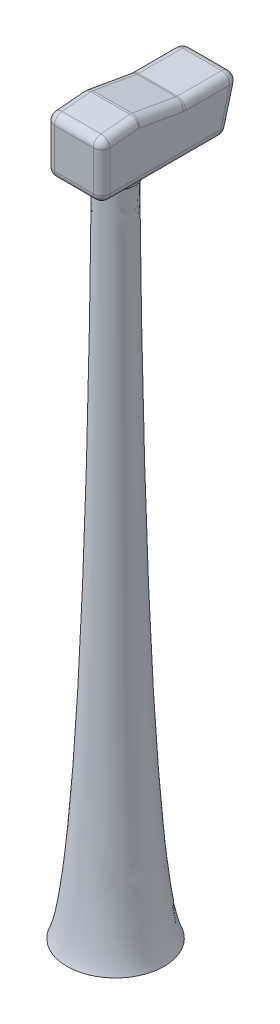
SolidWorks part; units mm, degrees
ref_plane "Ebene vorne" through (0, 0, 0) normal (0, 0, 1) x (1, 0, 0)
ref_plane "Ebene oben" through (0, 0, 0) normal (0, 1, 0) x (1, 0, 0)
ref_plane "Ebene rechts" through (0, 0, 0) normal (1, 0, 0) x (0, 0, -1)
sketch "Skizze2" plane through (0, 0, 0) normal (1, 0, 0) x (0, 0, -1)
  line L0 (3000, -4000) -> (3000, 4000)
  line L1 (-3000, -2000) -> (3000, -2000) construction
  line L2 (-3000, -2000) -> (-3000, 2000) construction
  line L3 (-3000, 2000) -> (3000, 2000) construction
  line L4 (3000, -2000) -> (3000, 2000) construction
  line L5 (-3000, -2000) -> (3000, 2000) construction
  line L6 (-3000, 2000) -> (3000, -2000) construction
  line L7 (3000, 4000) -> (8400, 4472.4388)
  line L8 (8400, 4472.4388) -> (15000, 3308.6807)
  line L9 (15000, 3308.6807) -> (23000, 3308.6807)
  line L10 (23000, 3308.6807) -> (21041.6449, -4000)
  line L11 (21041.6449, -4000) -> (3000, -4000)
  point P0 (0, 0)
  dimension "D1" = 6000
  dimension "D2" = 4000
  dimension "D3" = 20000
  dimension "D4" = 75
  dimension "D5" = 5400
  dimension "D6" = 6600
  dimension "D7" = 95
  dimension "D8" = 165
  dimension "D9" = 2000
  dimension "D10" = 2000
extrude "Aufsatz-Linear austragen1" add sketch "Skizze2" along normal blind 4000 and the other way blind 4000 contours L8 L9 L10 L11 L0 L7
fillet "Verrundung1" radius 1200 18 edges at (-4000, 3308.6807, -19000) (0, 3308.6807, -23000) (4000, 3308.6807, -19000) (-4000, 3890.5597, -11700) (0, 3308.6807, -15000) (4000, 3890.5597, -11700) (-4000, 4236.2194, -5700) (0, 4472.4388, -8400) (4000, 4236.2194, -5700) (0, 4000, -3000) (0, -4000, -3000) (-4000, 0, -3000) (-4000, -4000, -12020.8225) (-4000, -345.6596, -22020.8225) (0, -4000, -21041.6449) (4000, -345.6596, -22020.8225) (4000, -4000, -12020.8225) (4000, 0, -3000)
sketch "Skizze3" plane through (0, 0, 0) normal (1, 0, 0) x (0, 0, -1)
  line L0 (4200, -2800) -> (20120.8525, -2800) construction
  line L1 (6200, -2800) -> (9000, -2800)
  line L2 (6200, -2800) -> (6200, -4800)
  line L5 (-816.0524, 0) -> (6168.6291, 0) construction
  line L6 (9000, 0) -> (9000, -100000) construction
  line L7 (3000, -2800) -> (3000, 2900.4026) construction
  line L9 (9000, -100000) -> (2000, -100000)
  line L10 (9000, -2800) -> (9000, -100000)
  line L11 (6400, -4800) -> (6400, -4000)
  line L12 (20120.8525, -4000) -> (4200, -4000) construction
  line L13 (6400, -4000) -> (6520, -4000)
  line L14 (6520, -4000) -> (6520, -4800)
  line L15 (6400, -4800) -> (6200, -4800)
  line L16 (962.3284, -4800) -> (6520, -4800) construction
  spline S0 degree 3 poles (6520, -4800) (6520, -5632.5048) (6182.4784, -90939.9064) (2000, -100000) knots 0 0 0 0 1 1 1 1
  dimension "D1" = 6000
  dimension "D2" = 7000
  dimension "D3" = 100000
  dimension "D4" = 3500
  dimension "D5" = 60000
  dimension "D6" = 2000
  dimension "D7" = 2800
  dimension "D8" = 200
  dimension "D9" = 120
revolve "Rotation1" add sketch "Skizze3" angle 360 about L6
equation "\"hubDiameter\"=1"
